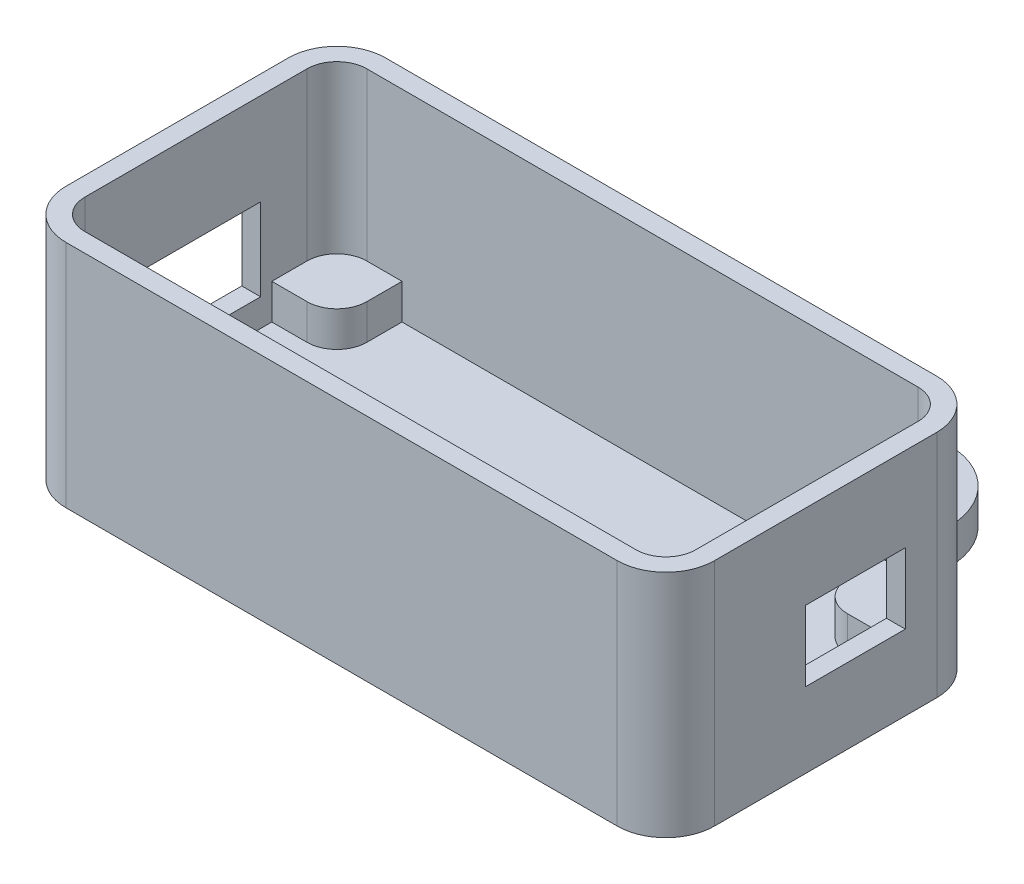
SolidWorks part; units mm, degrees
ref_plane "Front Plane" through (0, 0, 0) normal (0, 0, 1) x (1, 0, 0)
ref_plane "Top Plane" through (0, 0, 0) normal (0, 1, 0) x (1, 0, 0)
ref_plane "Right Plane" through (0, 0, 0) normal (1, 0, 0) x (0, 0, -1)
sketch "Sketch1" plane through (0, 0, 0) normal (0, 1, 0) x (1, 0, 0)
  line L0 (2.54, 25.6) -> (49.46, 25.6)
  line L1 (2.54, 0) -> (49.46, 0)
  line L2 (0, 2.54) -> (0, 21.46)
  line L3 (2.54, 24) -> (49.46, 24)
  line L4 (52, 2.54) -> (52, 21.46)
  line L5 (53.6, 2.54) -> (53.6, 21.46)
  line L6 (2.54, -1.6) -> (49.46, -1.6)
  line L7 (-1.6, 2.54) -> (-1.6, 21.46)
  line L16 (49.46, 24) -> (52, 24) construction
  line L17 (52, 24) -> (52, 21.46) construction
  arc A0 (52, 2.54) -> (49.46, 0) centre (49.46, 2.54) cw
  arc A1 (2.54, 0) -> (0, 2.54) centre (2.54, 2.54) cw
  arc A2 (0, 21.46) -> (2.54, 24) centre (2.54, 21.46) cw
  arc A3 (49.46, 24) -> (52, 21.46) centre (49.46, 21.46) cw
  arc A4 (49.46, 25.6) -> (53.6, 21.46) centre (49.46, 21.46) cw
  arc A5 (53.6, 2.54) -> (49.46, -1.6) centre (49.46, 2.54) cw
  arc A6 (2.54, -1.6) -> (-1.6, 2.54) centre (2.54, 2.54) cw
  arc A7 (-1.6, 21.46) -> (2.54, 25.6) centre (2.54, 21.46) cw
  point P5 (74.1384, 24)
  point P8 (26, 24)
  point P9 (52, 0)
  point P11 (26, 0)
  point P13 (0, 0)
  point P14 (52, 12)
  point P17 (0, 12)
  point P18 (0, -14.4114)
  point P19 (0, 24)
  point P34 (0, 39.8864)
  point P35 (71.0282, 24)
  point P36 (52, 36.1766)
  point P38 (52, -11.8258)
  point P39 (-28.4135, 0)
  point P40 (64.2832, 0)
  point P44 (49.8696, 21.8857)
  point P45 (50.2568, 22.3902)
  point P47 (48.8312, 21.2227)
  point P48 (48.9585, 20.5243)
  dimension "D3" = 2.54
  dimension "D1" = 52
  dimension "D2" = 24
  dimension "D4" = 1.6
extrude "Boss-Extrude1" add sketch "Sketch1" against normal blind 2.4 contours L0 A4 L5 A5 L6 A6 L7 A7
extrude "Boss-Extrude2" add sketch "Sketch1<3>" along normal blind 17.17 contours A7 L7 A6 L6 A5 L5 A4 L0 L3 A3 L4 A0 L1 A1 L2 A2 region at (26, 0, -24.9846)
sketch "Sketch1<3>" plane through (0, 0, 0) normal (0, 1, 0) x (1, 0, 0) same geometry as "Sketch1"
sketch "Sketch2" plane through (0, 0, 0) normal (0, 1, 0) x (1, 0, 0)
  line L0 (0, 18.46) -> (3, 18.46)
  line L1 (0, 2.54) -> (0, 21.46) construction
  line L2 (2.54, 24) -> (49.46, 24) construction
  line L3 (5.54, 24) -> (5.54, 21)
  line L4 (0, 18.46) -> (0, 24)
  line L5 (0, 24) -> (5.54, 24)
  arc A0 (3, 18.46) -> (5.54, 21) centre (3, 21) ccw
  dimension "D1" = 2.54
  dimension "D2" = 3
extrude "Boss-Extrude4" add sketch "Sketch2" along normal blind 3
ref_plane "Plane1" through (26, 0, 0) normal (-1, 0, 0) x (0, 0, 1)
ref_plane "Plane2" through (0, 0, -12) normal (0, 0, 1) x (1, 0, 0)
mirror "Mirror1" about plane through (26, 0, 0) normal (-1, 0, 0) of "Boss-Extrude4"
mirror "Mirror2" about plane through (0, 0, -12) normal (0, 0, 1) of "Boss-Extrude4", "Mirror1"
sketch "Sketch4" plane through (0, 0, 0) normal (1, 0, 0) x (0, 0, -1)
  line L0 (2.54, 3) -> (21.46, 3) construction
  line L1 (12, 3) -> (12, 5.84) construction
  line L3 (6.5, 9.34) -> (17.5, 9.34)
  line L4 (6.5, 9.34) -> (6.5, 2.34)
  line L5 (6.5, 2.34) -> (17.5, 2.34)
  line L6 (17.5, 9.34) -> (17.5, 2.34)
  line L7 (6.5, 9.34) -> (17.5, 2.34) construction
  line L8 (6.5, 2.34) -> (17.5, 9.34) construction
  point P10 (0, 0)
  point P11 (13.8795, 10.4219)
  dimension "D1" = 11
  dimension "D2" = 7
  dimension "D3" = 2.84
extrude "Cut-Extrude1" cut sketch "Sketch4" against normal through all
sketch "Sketch5" plane through (52, 0, 0) normal (-1, 0, 0) x (0, 0, 1)
  line L0 (-24, 3) -> (0, 3) construction
  line L1 (-14.53, 7) -> (-14.53, 3) construction
  line L2 (-18.78, 4) -> (-10.28, 4)
  line L3 (-18.78, 4) -> (-18.78, 10)
  line L4 (-18.78, 10) -> (-10.28, 10)
  line L5 (-10.28, 4) -> (-10.28, 10)
  line L6 (-18.78, 4) -> (-10.28, 10) construction
  line L7 (-18.78, 10) -> (-10.28, 4) construction
  point P4 (-14.53, 7)
  point P13 (-24, 3)
  point P15 (0, 3)
  dimension "D1" = 8.5
  dimension "D2" = 6
  dimension "D3" = 9.47
  dimension "D4" = 4
extrude "Cut-Extrude2" cut sketch "Sketch5" against normal through all
sketch "Sketch6" plane through (0, 0, 0) normal (0, 1, 0) x (1, 0, 0)
  line L1 (7.5, 31.6) -> (19.5, 31.6) construction
  line L2 (7.5, 31.6) -> (7.5, 25.6)
  line L3 (7.5, 25.6) -> (19.5, 25.6)
  line L4 (19.5, 31.6) -> (19.5, 25.6)
  line L10 (13.5, 25.6) -> (38.5, 25.6) construction
  line L11 (2.54, 25.6) -> (49.46, 25.6) construction
  arc A0 (7.5, 31.6) -> (19.5, 31.6) centre (13.5, 31.6) cw
  circle A1 centre (13.5, 31.6) radius 3.05
  point P6 (13.5, 25.6)
  point P16 (26, 25.6)
  point P17 (26, 25.6)
  dimension "D2" = 6
  dimension "D3" = 6.1
  dimension "D4" = 25
  dimension "D1" = 6
extrude "Boss-Extrude5" add sketch "Sketch6" against normal up to surface (2.4 mm away) up to face at (26, -2.4, -12)
extrude "Boss-Extrude6" add sketch "Sketch6<2>" along normal blind 0.6
sketch "Sketch6<2>" plane through (0, 0, 0) normal (0, 1, 0) x (1, 0, 0) same geometry as "Sketch6"
mirror "Mirror3" about plane through (26, 0, 0) normal (-1, 0, 0) of "Boss-Extrude6", "Boss-Extrude5"
